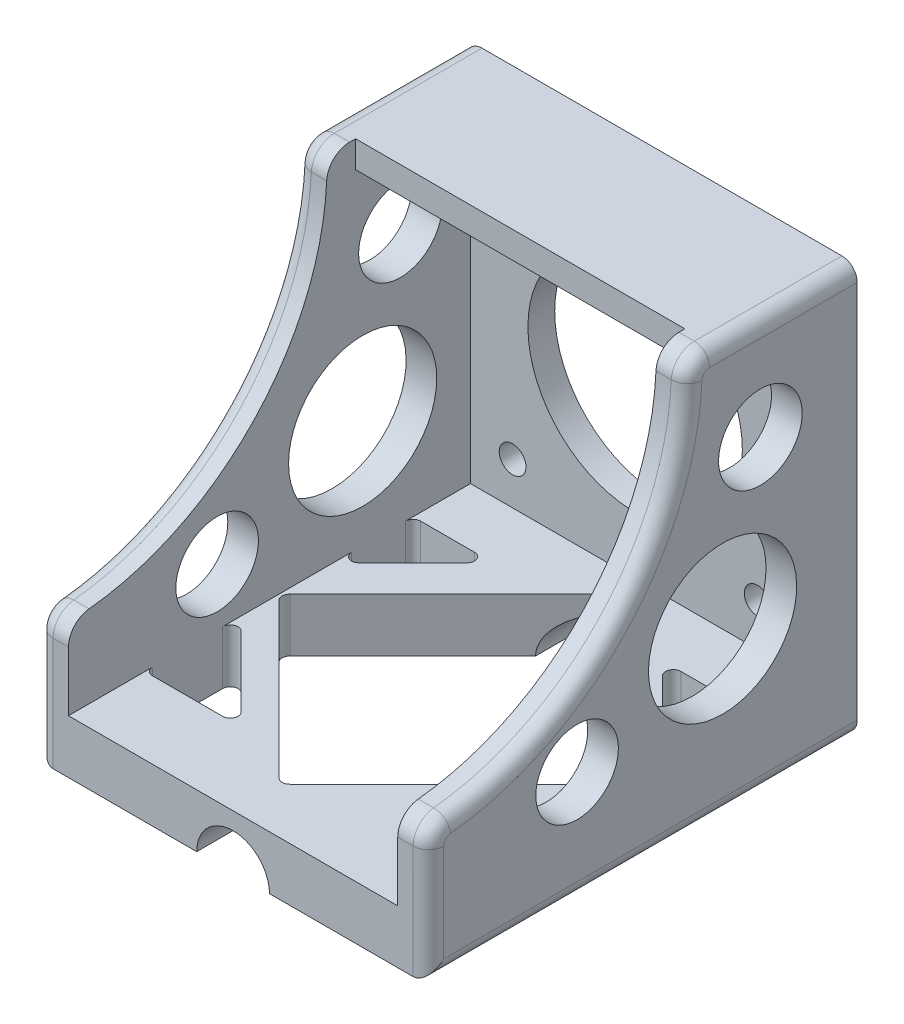
SolidWorks part; units mm, degrees
ref_plane "Front Plane" through (0, 0, 0) normal (0, 0, 1) x (1, 0, 0)
ref_plane "Top Plane" through (0, 0, 0) normal (0, 1, 0) x (1, 0, 0)
ref_plane "Right Plane" through (0, 0, 0) normal (1, 0, 0) x (0, 0, -1)
sketch "Sketch1" plane through (0, 0, 0) normal (0, 0, 1) x (1, 0, 0)
  line L1 (-51.9324, 28.7717) -> (-0.9324, 28.7717)
  line L2 (-51.9324, 28.7717) -> (-51.9324, -24.7283)
  line L3 (-51.9324, -24.7283) -> (-0.9324, -24.7283)
  line L4 (-0.9324, 28.7717) -> (-0.9324, -24.7283)
  dimension "D1" = 51
  dimension "D2" = 53.5
extrude "Boss-Extrude1" add sketch "Sketch1" along normal blind 56
sketch "Sketch2" plane through (0, 0, 56) normal (0, 0, 1) x (1, 0, 0)
  line L0 (-0.9324, -24.7283) -> (-0.9324, 28.7717) construction
  line L1 (-47.9324, -17.7283) -> (-4.9324, -17.7283)
  line L2 (-47.9324, -17.7283) -> (-47.9324, 25.2717)
  line L3 (-47.9324, 25.2717) -> (-4.9324, 25.2717)
  line L4 (-4.9324, -17.7283) -> (-4.9324, 25.2717)
  line L6 (-51.9324, -24.7283) -> (-0.9324, -24.7283) construction
  dimension "D1" = 43
  dimension "D2" = 43
  dimension "D3" = 4
  dimension "D4" = 7
extrude "Cut-Extrude1" cut sketch "Sketch2" against normal offset from surface (52.5 mm away) 3.5 up to face at (-26.4324, 2.0217, 0)
sketch "Sketch3" plane through (0, 0, 56) normal (0, 0, 1) x (1, 0, 0)
  line L0 (-0.9324, 28.7717) -> (-51.9324, 28.7717) construction
  line L1 (-47.9324, 25.2717) -> (-4.9324, 25.2717)
  line L2 (-47.9324, 25.2717) -> (-47.9324, 28.7717)
  line L3 (-47.9324, 28.7717) -> (-4.9324, 28.7717)
  line L4 (-4.9324, 25.2717) -> (-4.9324, 28.7717)
extrude "Cut-Extrude2" cut sketch "Sketch3" against normal offset from surface (37.5 mm away) 18.5 up to face at (-26.4324, 2.0217, 0)
sketch "Sketch4" plane through (-51.9324, 0, 0) normal (-1, 0, 0) x (0, 0, 1)
  line L1 (56, 28.7717) -> (56, -24.7283) construction
  line L2 (56, 28.7717) -> (0, 28.7717) construction
  line L3 (22.267, 28.7717) -> (56, 28.7717)
  line L4 (56, 28.7717) -> (56, -7.1627)
  arc A0 (22.267, 28.7717) -> (56, -7.1627) centre (56.8636, 27.4485) ccw
extrude "Cut-Extrude3" cut sketch "Sketch4" against normal blind 76
fillet "Fillet1" radius 3 4 edges at (-2.9324, 28.7717, 22.267) (-49.9324, 28.7717, 22.267) (-49.9324, -7.1627, 56) (-2.9324, -7.1627, 56)
sketch "Sketch5" plane through (-51.9324, 0, 0) normal (-1, 0, 0) x (0, 0, 1)
  circle A0 centre (17.58, -3.5992) radius 9.6731
  circle A1 centre (36.5792, -10.3047) radius 5.3908
  circle A2 centre (12.6494, 15.5973) radius 5.4569
extrude "Cut-Extrude4" cut sketch "Sketch5" against normal blind 76
sketch "Sketch6" plane through (0, 0, 3.5) normal (0, 0, 1) x (1, 0, 0)
  line L0 (-4.9324, 25.2717) -> (-47.9324, -17.7283) construction
  line L1 (-4.9324, -17.7283) -> (-47.9324, 25.2717) construction
  circle A0 centre (-26.4324, 3.7717) radius 14
  circle A1 centre (-10.4324, 19.7717) radius 1.75
  circle A2 centre (-42.4324, 19.7717) radius 1.75
  circle A3 centre (-42.4324, -12.2283) radius 1.75
  circle A4 centre (-10.4324, -12.2283) radius 1.75
  dimension "D2" = 28
  dimension "D3" = 3.5
  dimension "D1" = 32
extrude "Cut-Extrude5" cut sketch "Sketch6" against normal blind 76
sketch "Sketch7" plane through (0, 0, 0) normal (0, 0, -1) x (-1, 0, 0)
  line L0 (51.9324, -24.7283) -> (0.9324, -24.7283) construction
  circle A0 centre (26.4324, -24.7283) radius 4.75
extrude "Cut-Extrude6" cut sketch "Sketch7" against normal blind 76
sketch "Sketch8" plane through (0, -24.7283, 0) normal (0, -1, 0) x (1, 0, 0)
  line L0 (-26.4324, 56) -> (-26.4324, 0) construction
  line L1 (-21.6824, 56) -> (-31.1824, 56) construction
  line L2 (-31.1824, 0) -> (-21.6824, 0) construction
  line L3 (-26.4324, 50) -> (-4.9324, 28.5)
  line L4 (-4.9324, 3.5) -> (-4.9324, 56) construction
  line L5 (-4.9324, 28.5) -> (-26.4324, 7)
  line L7 (-26.4324, 7) -> (-47.9324, 28.5)
  line L8 (-47.9324, 28.5) -> (-26.4324, 50)
  line L9 (-47.9324, 3.5) -> (-47.9324, 56) construction
  line L10 (-26.4324, 7) -> (-4.9324, 7) construction
  line L11 (-26.4324, 7) -> (-47.9324, 7) construction
  line L12 (-26.4324, 50) -> (-47.9324, 50) construction
  line L13 (-26.4324, 50) -> (-4.9324, 50) construction
  line L14 (-15.3613, 46) -> (-4.9324, 46)
  line L15 (-4.9324, 46) -> (-4.9324, 35.5711)
  line L16 (-4.9324, 35.5711) -> (-15.3613, 46)
  line L17 (-4.9324, 11) -> (-15.3613, 11)
  line L18 (-15.3613, 11) -> (-4.9324, 21.4289)
  line L19 (-4.9324, 21.4289) -> (-4.9324, 11)
  line L20 (-47.9324, 11) -> (-37.5034, 11)
  line L21 (-37.5034, 11) -> (-47.9324, 21.4289)
  line L22 (-47.9324, 21.4289) -> (-47.9324, 11)
  line L23 (-47.9324, 46) -> (-35.3821, 46)
  line L24 (-35.3821, 46) -> (-47.9324, 33.4497)
  line L25 (-47.9324, 33.4497) -> (-47.9324, 46)
  dimension "D1" = 6
  dimension "D2" = 45
  dimension "D3" = 4
  dimension "D4" = 45
  dimension "D5" = 5
  dimension "D6" = 4
  dimension "D7" = 5
  dimension "D8" = 5
extrude "Cut-Extrude7" cut sketch "Sketch8" against normal blind 27
fillet "Fillet2" radius 1 16 edges at (-47.9324, -21.2283, 33.4497) (-4.9324, -21.2283, 35.5711) (-4.9324, -21.2283, 21.4289) (-47.9324, -21.2283, 21.4289) (-15.3613, -21.2283, 11) (-37.5034, -21.2283, 11) (-26.4324, -18.8533, 7) (-4.9324, -21.2283, 11) (-47.9324, -21.2283, 11) (-47.9324, -21.2283, 28.5) (-4.9324, -21.2283, 28.5) (-4.9324, -21.2283, 46) (-47.9324, -21.2283, 46) (-35.3821, -21.2283, 46) (-15.3613, -21.2283, 46) (-26.4324, -18.8533, 50)
fillet "Fillet3" radius 2 12 edges at (-51.9324, 28.7717, 9.6395) (-51.9324, 27.9398, 21.3526) (-51.9324, -17.3514, 56) (-51.9324, -7.9651, 55.2276) (-0.9324, 28.7717, 9.6395) (-0.9324, 27.9398, 21.3526) (-0.9324, -17.3514, 56) (-0.9324, -7.9651, 55.2276) (-51.9324, 3.6909, 31.6792) (-0.9324, 3.6909, 31.6792) (-51.9324, -24.7283, 28) (-0.9324, -24.7283, 28)
